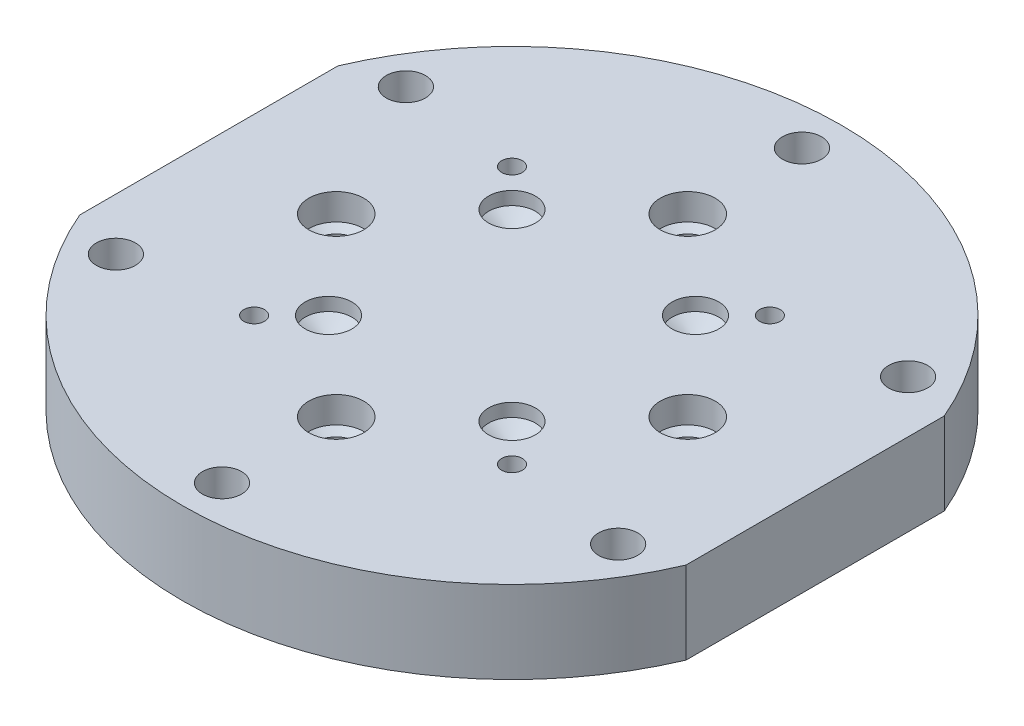
SolidWorks part; units mm, degrees
material "Copper"
ref_plane "Front Plane" through (0, 0, 0) normal (0, 0, 1) x (1, 0, 0)
ref_plane "Top Plane" through (0, 0, 0) normal (0, 1, 0) x (1, 0, 0)
ref_plane "Right Plane" through (0, 0, 0) normal (1, 0, 0) x (0, 0, -1)
ref_axis "Y Axis" through (0, 0.1588, 0) along (0, -1, 0)
sketch "outer" plane through (0, 0, 0) normal (0, 1, 0) x (1, 0, 0)
  circle A0 centre (0, 0) radius 19.05
  dimension "D1" = 38.1
extrude "Body" add sketch "outer" against normal blind 4.7625
sketch "Screw Position" plane through (0, 0, 0) normal (0, 1, 0) x (1, 0, 0)
  point P0 (0, -16.764)
  dimension "D1" = 16.764
hole_wizard "#4-40 Tapped Hole" positions "Sketch12" profile "Sketch13" tap size "#4-40" standard "ANSI Inch" end condition through all
sketch "Sketch12" plane through (0, 0, 0) normal (0, 1, 0) x (1, 0, 0)
  point P0 (0, -16.764)
sketch "Sketch13" plane through (0, 0, 16.764) normal (1, 0, 0) x (0, 0, 1)
  line L0 (0, 0) -> (0, 4.7625)
  line L1 (0, 4.7625) -> (1.1303, 4.7625)
  line L2 (1.1303, 4.7625) -> (1.1303, 0)
  line L5 (1.1303, 0) -> (0, 0)
  line L11 (0, -6.35) -> (0, 107.95) construction
  dimension "Thru Tap Drill Dia." = 2.2606
  dimension "Thru Tap Drill Depth" = 4.7625
cosmetic thread "Hole Thread3" parameters "D2"=2.8448
pattern_circular "Screw Holes" count 6 over 360 about axis through (0, 0.1588, 0) along (0, -1, 0) of "#4-40 Tapped Hole"
sketch "inner" plane through (0, 0, 0) normal (0, 1, 0) x (1, 0, 0)
  circle A0 centre (0, 0) radius 11.938
  dimension "D1" = 23.876
sketch "Inner Screw Position" plane through (0, 0, 0) normal (0, 1, 0) x (1, 0, 0)
  point P0 (-7.4536, 7.4536)
  dimension "D1" = 10.541
hole_wizard "#0-80 Tapped Hole" positions "Sketch34" profile "Sketch35" tap size "#0-80" standard "ANSI Inch" end condition through all
sketch "Sketch34" plane through (0, 0, 0) normal (0, 1, 0) x (1, 0, 0)
  point P0 (-7.4536, 7.4536)
sketch "Sketch35" plane through (-7.4536, 0, -7.4536) normal (1, 0, 0) x (0, 0, 1)
  line L0 (0, 0) -> (0, 4.7625)
  line L1 (0, 4.7625) -> (0.5956, 4.7625)
  line L2 (0.5956, 4.7625) -> (0.5956, 0)
  line L5 (0.5956, 0) -> (0, 0)
  line L11 (0, -6.35) -> (0, 107.95) construction
  dimension "Thru Tap Drill Dia." = 1.1913
  dimension "Thru Tap Drill Depth" = 4.7625
cosmetic thread "Hole Thread4" parameters "D2"=1.524
pattern_circular "Inner Screw Holes" count 4 over 360 about axis through (0, 0.1588, 0) along (0, -1, 0) of "#0-80 Tapped Hole"
sketch "IO Hole Location" plane through (0, 0, 0) normal (0, 1, 0) x (1, 0, 0)
  point P0 (0, 10.16)
hole_wizard "#43 (0.089) Diameter Hole1" positions "Sketch36" profile "Sketch37" hole size "#43" standard "ANSI Inch" end condition through all
sketch "Sketch36" plane through (0, 0, 0) normal (0, 1, 0) x (1, 0, 0)
  point P0 (0, 10.16)
sketch "Sketch37" plane through (0, 0, -10.16) normal (1, 0, 0) x (0, 0, 1)
  line L0 (0, 0) -> (0, 4.7625)
  line L1 (0, 4.7625) -> (1.1303, 4.7625)
  line L2 (1.1303, 4.7625) -> (1.1303, 0)
  line L5 (1.1303, 0) -> (0, 0)
  line L11 (0, -6.35) -> (0, 107.95) construction
  dimension "Thru Hole Dia." = 2.2606
  dimension "Thru Hole Depth" = 4.7625
hole_wizard "1/8 (0.125) Diameter Hole1" positions "Sketch38" profile "Sketch40" hole size "1/8" standard "ANSI Inch"
sketch "Sketch38" plane through (0, 0, 0) normal (0, 1, 0) x (1, 0, 0)
  point P0 (0, 10.16)
sketch "Sketch40" plane through (0, 0, -10.16) normal (1, 0, 0) x (0, 0, 1)
  line L0 (0, 0) -> (0, 2.4779)
  line L1 (0, 2.4779) -> (1.5875, 1.524)
  line L2 (1.5875, 1.524) -> (1.5875, 0)
  line L5 (1.5875, 0) -> (0, 0)
  line L10 (0, 2.4779) -> (-1.5875, 1.524) construction
  line L11 (0, -6.35) -> (0, 107.95) construction
  dimension "Hole Dia." = 3.175
  dimension "Hole Depth" = 1.524
  dimension "Drill Angle" = 118
hole_wizard "1/8 (0.125) Diameter Hole2" positions "Sketch41" profile "Sketch42" hole size "1/8" standard "ANSI Inch"
sketch "Sketch41" plane through (0, -4.7625, 0) normal (0, -1, 0) x (-1, 0, 0)
  point P0 (0, 10.16)
sketch "Sketch42" plane through (0, -4.7625, -10.16) normal (1, 0, 0) x (0, 0, -1)
  line L0 (0, 0) -> (0, 2.4779)
  line L1 (0, 2.4779) -> (1.5875, 1.524)
  line L2 (1.5875, 1.524) -> (1.5875, 0)
  line L5 (1.5875, 0) -> (0, 0)
  line L10 (0, 2.4779) -> (-1.5875, 1.524) construction
  line L11 (0, -6.35) -> (0, 107.95) construction
  dimension "Hole Dia." = 3.175
  dimension "Hole Depth" = 1.524
  dimension "Drill Angle" = 118
pattern_circular "IO Holes Pattern" count 4 over 360 about axis through (0, 0.1588, 0) along (0, -1, 0) of "#43 (0.089) Diameter Hole1", "1/8 (0.125) Diameter Hole1", "1/8 (0.125) Diameter Hole2"
sketch "Post Bottom Location" plane through (0, 0, 0) normal (0, 1, 0) x (1, 0, 0)
  point P0 (0, 7)
  point P1 (-5.3033, 5.3033)
  dimension "D1" = 7
  dimension "D2" = 7.5
hole_wizard "#36 (0.1065) Diameter Hole1" positions "Sketch44" profile "Sketch45" hole size "#36" standard "ANSI Inch"
sketch "Sketch44" plane through (0, 0, 0) normal (0, 1, 0) x (1, 0, 0)
  point P3 (-5.3033, 5.3033)
sketch "Sketch45" plane through (-5.3033, 0, -5.3033) normal (1, 0, 0) x (0, 0, 1)
  line L0 (0, 0) -> (0, 1.5747)
  line L1 (0, 1.5747) -> (1.3525, 0.762)
  line L2 (1.3525, 0.762) -> (1.3525, 0)
  line L5 (1.3525, 0) -> (0, 0)
  line L10 (0, 1.5747) -> (-1.3525, 0.762) construction
  line L11 (0, -6.35) -> (0, 107.95) construction
  dimension "Hole Dia." = 2.7051
  dimension "Hole Depth" = 0.762
  dimension "Drill Angle" = 118
pattern_circular "Post Bottoms" count 4 over 360 about axis through (0, 0.1588, 0) along (0, -1, 0) of "#36 (0.1065) Diameter Hole1"
sketch "Flat Cut Sketch" plane through (0, 0, 0) normal (0, 1, 0) x (1, 0, 0)
  line L0 (-20.574, 19.05) -> (-17.526, 19.05)
  line L1 (20.574, -19.05) -> (17.526, -19.05)
  line L2 (20.574, -19.05) -> (20.574, 19.05)
  line L3 (20.574, 19.05) -> (17.526, 19.05)
  line L4 (17.526, -19.05) -> (17.526, 19.05)
  line L5 (20.574, -19.05) -> (17.526, 19.05) construction
  line L6 (20.574, 19.05) -> (17.526, -19.05) construction
  line L7 (-20.574, 19.05) -> (-20.574, -19.05)
  line L8 (-20.574, -19.05) -> (-17.526, -19.05)
  line L9 (-17.526, 19.05) -> (-17.526, -19.05)
  line L10 (-20.574, 19.05) -> (-17.526, -19.05) construction
  line L11 (-20.574, -19.05) -> (-17.526, 19.05) construction
  circle A0 centre (0, 0) radius 19.05 construction
  point P1 (19.05, 0)
  point P3 (19.05, 0)
  point P11 (-19.05, 0)
  point P12 (-19.05, 0)
  point P17 (0, 0)
  dimension "D2" = 38.1
  dimension "D3" = 2
extrude "Cut-Extrude1" cut sketch "Flat Cut Sketch" against normal through all and the other way through all
equation "\"outer_d\"= 3 / 2in"
equation "\"screw_r\"= 0.66in"
equation "\"inner_d\"= 0.940in"
equation "\"bottom_h\"= 3 / 16in"
equation "\"pocket_h\"= 0.060in"
equation "\"screw_inner_r\"= 0.415in"
equation "\"io_r\"= 0.4in"
equation "\"D1@outer\" = \"outer_d\""
equation "\"D1@Body\" = \"bottom_h\""
equation "\"D1@inner\" = \"inner_d\""
equation "\"D1@Screw Position\" = \"screw_r\""
equation "\"D1@Inner Screw Position\" = \"screw_inner_r\""
equation "\"D1@IO Hole Location\"=\"io_r\""
equation "\"post_r1\"= 7mm"
equation "\"post_r2\"= 7.5mm"
equation "\"D1@Post Bottom Location\" = \"post_r1\""
equation "\"D2@Post Bottom Location\" = \"post_r2\""
equation "\"post_bottom_h\"= 0.03in"
equation "\"cut\"= 0.06in"
equation "\"D2@Flat Cut Sketch\"=\"outer_d\""
equation "\"D1@Flat Cut Sketch\"=2 * \"cut\""
